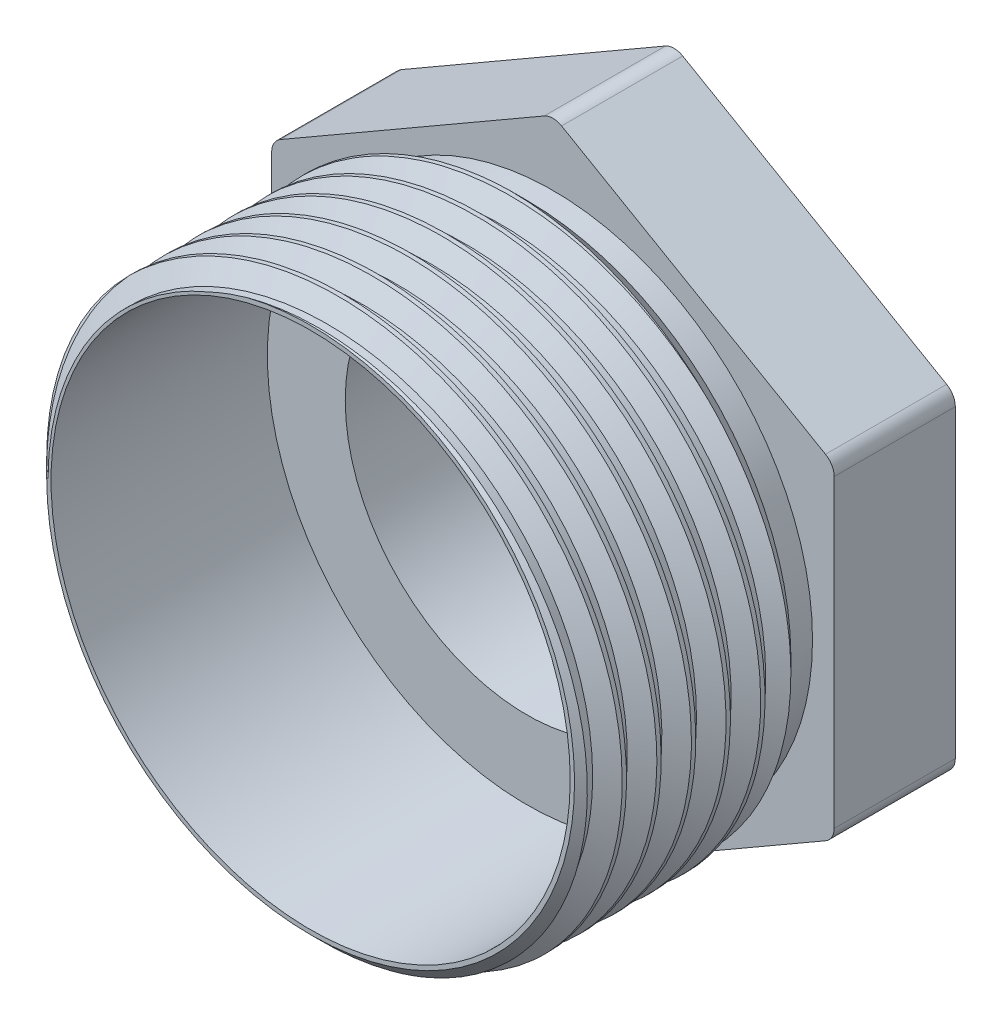
SolidWorks part; units mm, degrees
note: The reader was unsure of these and kept them because the rebuilt part matched: shared geometry of "Sketch1<7>", "Sketch1<8>".
ref_plane "Front Plane" through (0, 0, 0) normal (0, 0, 1) x (1, 0, 0)
ref_plane "Top Plane" through (0, 0, 0) normal (0, 1, 0) x (1, 0, 0)
ref_plane "Right Plane" through (0, 0, 0) normal (1, 0, 0) x (0, 0, -1)
sketch "Sketch1" plane through (0, 0, 0) normal (0, 0, 1) x (1, 0, 0)
  line L1 (32.5, -18.7639) -> (32.5, 18.7639)
  line L2 (32.5, 18.7639) -> (0, 37.5278)
  line L3 (0, 37.5278) -> (-32.5, 18.7639)
  line L4 (-32.5, 18.7639) -> (-32.5, -18.7639)
  line L5 (-32.5, -18.7639) -> (0, -37.5278)
  line L6 (0, -37.5278) -> (32.5, -18.7639)
  circle A0 centre (0, 0) radius 32.5 construction
  circle A1 centre (0, 0) radius 30
  circle A2 centre (0, 0) radius 21
  circle A3 centre (0, 0) radius 32.5
  dimension "D1" = 65
  dimension "D2" = 42
  dimension "D3" = 60
  dimension "D4" = 65
extrude "Boss-Extrude1" add sketch "Sketch1" along normal blind 14 contours A3 A1 | A1 A2 | A3 L1 L2 | A3 L6 L1 | A3 L2 L3 | A3 L3 L4 | A3 L4 L5 | A3 L5 L6
extrude "Boss-Extrude5" add sketch "Sketch1<7>" along normal blind 17 contours A1 A2
sketch "Sketch1<7>" plane through (0, 0, 0) normal (0, 0, 1) x (1, 0, 0) same geometry as "Sketch1"
extrude "Boss-Extrude6" add sketch "Sketch1<8>" along normal blind 25 from surface at 17 separate body contours A3 A1 starting at face at (21, 0, 17)
sketch "Sketch1<8>" plane through (0, 0, 0) normal (0, 0, 1) x (1, 0, 0) same geometry as "Sketch1"
fillet "Fillet1" radius 2 6 edges at (0, -37.5278, 7) (-32.5, -18.7639, 7) (-32.5, 18.7639, 7) (32.5, 18.7639, 7) (32.5, -18.7639, 7) (0, 37.5278, 7)
chamfer "Chamfer1" distance 2 angle 45 2 edges at (32.5, 0, 17) (32.5, 0, 42)
thread "Thread1" pitch 4 start angle 0, offset 4, length 0, pitch 4, diameter 65
ref_plane "Plane4" through (-32.5, 0, 44) normal (0, -1, 0) x (-1, 0, 0)
sketch "Thread Profile3" plane through (-32.5, 0, 44) normal (0, -1, 0) x (-1, 0, 0)
  line L0 (0, 0) -> (0, 4) construction
  line L11 (0, 0) -> (0, 3.5)
  line L12 (0, 3.5) -> (-2.1651, 2.25)
  line L13 (-2.1651, 2.25) -> (-2.1651, 1.25)
  line L15 (-2.1651, 1.25) -> (0, 0)
  line L17 (-2.1651, 1.75) -> (0, 1.75) construction
  point P2 (0, 0)
  dimension "Pitch" = 4
  dimension "Profile_Angle" = 60
  dimension "Profile_Land" = 1
  dimension "Profile_Height" = 2.1651
